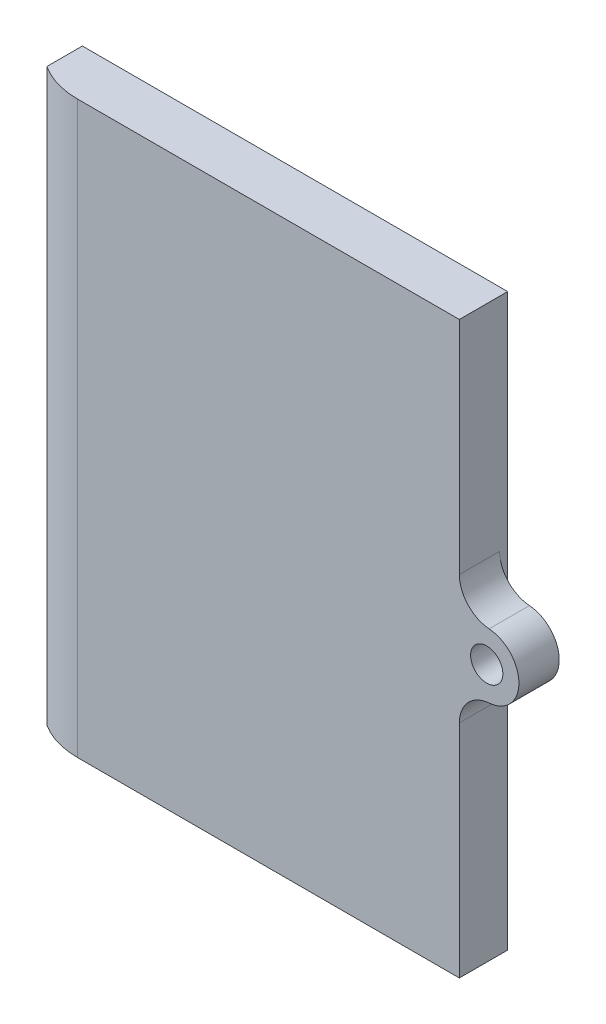
SolidWorks part; units mm, degrees
ref_plane "Front Plane" through (0, 0, 0) normal (0, 0, 1) x (1, 0, 0)
ref_plane "Top Plane" through (0, 0, 0) normal (0, 1, 0) x (1, 0, 0)
ref_plane "Right Plane" through (0, 0, 0) normal (1, 0, 0) x (0, 0, -1)
sketch "Sketch1" plane through (0, 0, 0) normal (0, 1, 0) x (1, 0, 0)
  line L0 (-17, 2.5) -> (-12, 2.5)
  line L1 (-12, 2.5) -> (12, 2.5)
  line L3 (-12, -2.5) -> (12, -2.5)
  line L4 (12, 2.5) -> (12, -2.5)
  line L5 (-12, 2.5) -> (12, -2.5) construction
  line L6 (-12, -2.5) -> (12, 2.5) construction
  arc A0 (-12, -2.5) -> (-17, 2.5) centre (-12, 2.5) cw
  point P0 (0, 0)
  dimension "D3" = 5
  dimension "D1" = 24
  dimension "D2" = 5
extrude "Boss-Extrude1" add sketch "Sketch1" along normal blind 35.4
sketch "Sketch2" plane through (0, 0, -2.5) normal (0, 0, -1) x (-1, 0, 0)
  line L0 (-12, 35.4) -> (-12, 0) construction
  line L1 (15, 39.4037) -> (43.6282, 39.4037)
  line L2 (15, 39.4037) -> (15, -5.1034)
  line L3 (15, -5.1034) -> (43.6282, -5.1034)
  line L4 (43.6282, 39.4037) -> (43.6282, -5.1034)
  dimension "D1" = 27
extrude "Cut-Extrude1" cut sketch "Sketch2" against normal blind 36
sketch "Sketch3" plane through (0, 35.4, 0) normal (0, 1, 0) x (1, 0, 0)
  line L0 (12, 2.5) -> (-15, 2.5) construction
  line L1 (12, 2.5) -> (-15, 2.5)
  line L2 (12, 2.5) -> (12, 0.5)
  line L3 (12, 0.5) -> (-15, 0.5)
  line L4 (-15, 2.5) -> (-15, 0.5)
  line L5 (-15, 2.5) -> (-15, -1.5) construction
  line L6 (12, -2.5) -> (12, 2.5) construction
  dimension "D1" = 2
extrude "Cut-Extrude2" cut sketch "Sketch3" against normal through all
sketch "Sketch4" plane through (0, 0, -0.5) normal (0, 0, -1) x (-1, 0, 0)
  line L0 (-12, 0) -> (-12, 35.4) construction
  line L1 (-16.3669, 38.6167) -> (-11.7, 38.6167)
  line L2 (-16.3669, 38.6167) -> (-16.3669, -1.2583)
  line L3 (-16.3669, -1.2583) -> (-11.7, -1.2583)
  line L4 (-11.7, 38.6167) -> (-11.7, -1.2583)
  line L5 (14.7, 39.0893) -> (21.1391, 39.0893)
  line L6 (14.7, 39.0893) -> (14.7, -2.0854)
  line L7 (14.7, -2.0854) -> (21.1391, -2.0854)
  line L8 (21.1391, 39.0893) -> (21.1391, -2.0854)
  line L9 (15, 0) -> (15, 35.4) construction
  dimension "D1" = 0.3
  dimension "D2" = 0.3
extrude "Cut-Extrude3" cut sketch "Sketch4" against normal through all
sketch "Sketch5" plane through (0, 0, 2.5) normal (0, 0, 1) x (1, 0, 0)
  line L0 (11.7, 35.4) -> (13.4, 35.4) construction
  line L1 (13.4, 35.4) -> (13.4, 0) construction
  line L2 (13.4, 0) -> (11.7, 0) construction
  line L3 (13.4, 19.7) -> (11.7, 19.7)
  line L4 (11.7, 0) -> (11.7, 35.4) construction
  line L5 (11.7, 19.7) -> (11.7, 15.7)
  line L6 (11.7, 15.7) -> (13.4, 15.7)
  arc A0 (13.4, 15.7) -> (13.4, 19.7) centre (13.4, 17.7) ccw
  circle A1 centre (13.4, 17.7) radius 1
  dimension "D2" = 4
  dimension "D3" = 2
  dimension "D1" = 1.7
extrude "Boss-Extrude2" add sketch "Sketch5" against normal offset from surface (2.5 mm away) 0.5 up to face at (-1.5, 17.7, -0.5)
fillet "Fillet1" radius 2 2 edges at (11.7, 15.7, 1.25) (11.7, 19.7, 1.25)
sketch "Sketch6" plane through (0, 0, -0.5) normal (0, 0, -1) x (-1, 0, 0)
  line L0 (14.7, 0) -> (14.7, 35.4) construction
  line L1 (14.7, 35.4) -> (-11.7, 35.4) construction
  line L2 (14.7, 0) -> (-11.7, 0) construction
  point P0 (14.7, 29.4)
  point P1 (14.7, 6)
  dimension "D1" = 6
  dimension "D2" = 6
